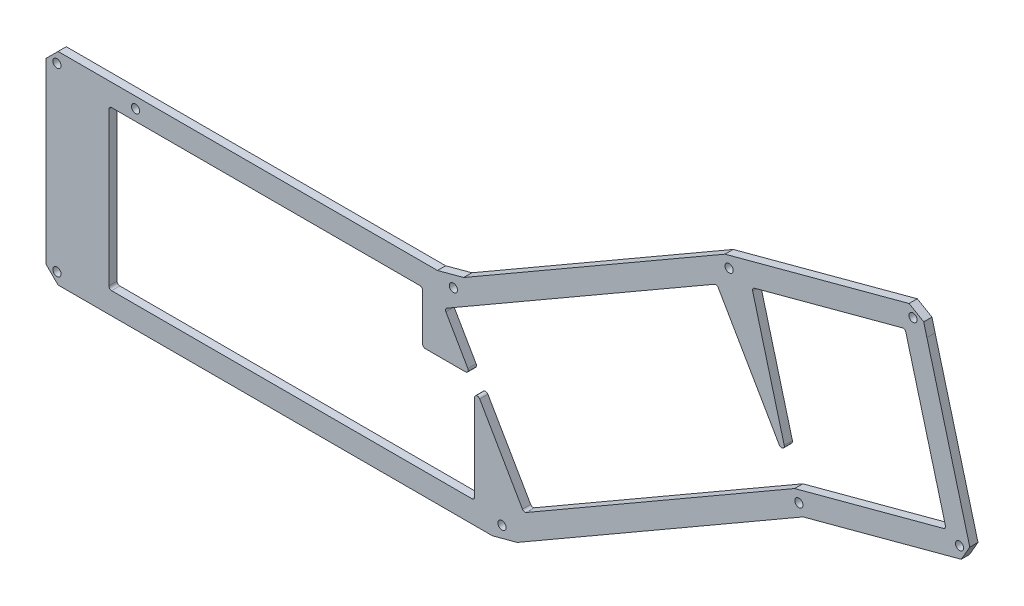
SolidWorks part; units mm, degrees
ref_plane "Plan de face" through (0, 0, 0) normal (0, 0, 1) x (1, 0, 0)
ref_plane "Plan de dessus" through (0, 0, 0) normal (0, 1, 0) x (1, 0, 0)
ref_plane "Plan de droite" through (0, 0, 0) normal (1, 0, 0) x (0, 0, -1)
sketch "Esquisse1" plane through (0, 0, 0) normal (0, 0, 1) x (1, 0, 0)
  line L0 (-73.9886, 18.0851) -> (-59.9886, 18.0851) construction
  line L1 (-73.9886, 37.0851) -> (-59.9886, 37.0851) construction
  line L2 (-73.9886, 37.0851) -> (-73.9886, 23.0851) construction
  line L3 (-73.9886, 23.0851) -> (-59.9886, 23.0851) construction
  line L4 (-59.9886, 37.0851) -> (-59.9886, 23.0851) construction
  line L5 (-73.9886, 18.0851) -> (-73.9886, 4.0851) construction
  line L6 (-73.9886, 4.0851) -> (-59.9886, 4.0851) construction
  line L7 (-59.9886, 18.0851) -> (-59.9886, 4.0851) construction
  line L8 (-73.9886, -0.9149) -> (-59.9886, -0.9149) construction
  line L9 (-73.9886, -0.9149) -> (-73.9886, -14.9149) construction
  line L10 (-73.9886, -14.9149) -> (-59.9886, -14.9149) construction
  line L11 (-59.9886, -0.9149) -> (-59.9886, -14.9149) construction
  line L12 (-73.9886, 37.0851) -> (-73.9886, 18.0851) construction
  line L13 (-54.9886, 18.0851) -> (-40.9886, 18.0851) construction
  line L14 (-54.9886, 37.0851) -> (-40.9886, 37.0851) construction
  line L15 (-54.9886, 37.0851) -> (-54.9886, 23.0851) construction
  line L16 (-54.9886, 23.0851) -> (-40.9886, 23.0851) construction
  line L17 (-40.9886, 37.0851) -> (-40.9886, 23.0851) construction
  line L18 (-54.9886, 18.0851) -> (-54.9886, 4.0851) construction
  line L19 (-54.9886, 4.0851) -> (-40.9886, 4.0851) construction
  line L20 (-40.9886, 18.0851) -> (-40.9886, 4.0851) construction
  line L21 (-54.9886, -0.9149) -> (-40.9886, -0.9149) construction
  line L22 (-54.9886, -0.9149) -> (-54.9886, -14.9149) construction
  line L23 (-54.9886, -14.9149) -> (-40.9886, -14.9149) construction
  line L24 (-40.9886, -0.9149) -> (-40.9886, -14.9149) construction
  line L25 (-54.9886, 37.0851) -> (-54.9886, 18.0851) construction
  line L26 (-35.9886, 18.0851) -> (-21.9886, 18.0851) construction
  line L27 (-35.9886, 37.0851) -> (-21.9886, 37.0851) construction
  line L28 (-35.9886, 37.0851) -> (-35.9886, 23.0851) construction
  line L29 (-35.9886, 23.0851) -> (-21.9886, 23.0851) construction
  line L30 (-21.9886, 37.0851) -> (-21.9886, 23.0851) construction
  line L31 (-35.9886, 18.0851) -> (-35.9886, 4.0851) construction
  line L32 (-35.9886, 4.0851) -> (-21.9886, 4.0851) construction
  line L33 (-21.9886, 18.0851) -> (-21.9886, 4.0851) construction
  line L34 (-35.9886, -0.9149) -> (-21.9886, -0.9149) construction
  line L35 (-35.9886, -0.9149) -> (-35.9886, -14.9149) construction
  line L36 (-35.9886, -14.9149) -> (-21.9886, -14.9149) construction
  line L37 (-21.9886, -0.9149) -> (-21.9886, -14.9149) construction
  line L38 (-35.9886, 37.0851) -> (-35.9886, 18.0851) construction
  line L39 (-16.9886, 18.0851) -> (-2.9886, 18.0851) construction
  line L40 (-16.9886, 37.0851) -> (-2.9886, 37.0851) construction
  line L41 (-16.9886, 37.0851) -> (-16.9886, 23.0851) construction
  line L42 (-16.9886, 23.0851) -> (-2.9886, 23.0851) construction
  line L43 (-2.9886, 37.0851) -> (-2.9886, 23.0851) construction
  line L44 (-16.9886, 18.0851) -> (-16.9886, 4.0851) construction
  line L45 (-16.9886, 4.0851) -> (-2.9886, 4.0851) construction
  line L46 (-2.9886, 18.0851) -> (-2.9886, 4.0851) construction
  line L47 (-16.9886, -0.9149) -> (-2.9886, -0.9149) construction
  line L48 (-16.9886, -0.9149) -> (-16.9886, -14.9149) construction
  line L49 (-16.9886, -14.9149) -> (-2.9886, -14.9149) construction
  line L50 (-2.9886, -0.9149) -> (-2.9886, -14.9149) construction
  line L51 (-16.9886, 37.0851) -> (-16.9886, 18.0851) construction
  line L52 (2.0114, 18.0851) -> (16.0114, 18.0851) construction
  line L53 (2.0114, 37.0851) -> (16.0114, 37.0851) construction
  line L54 (2.0114, 37.0851) -> (2.0114, 23.0851) construction
  line L55 (2.0114, 23.0851) -> (16.0114, 23.0851) construction
  line L56 (16.0114, 37.0851) -> (16.0114, 23.0851) construction
  line L57 (2.0114, 18.0851) -> (2.0114, 4.0851) construction
  line L58 (2.0114, 4.0851) -> (16.0114, 4.0851) construction
  line L59 (16.0114, 18.0851) -> (16.0114, 4.0851) construction
  line L60 (2.0114, -0.9149) -> (16.0114, -0.9149) construction
  line L61 (2.0114, -0.9149) -> (2.0114, -14.9149) construction
  line L62 (2.0114, -14.9149) -> (16.0114, -14.9149) construction
  line L63 (16.0114, -0.9149) -> (16.0114, -14.9149) construction
  line L64 (2.0114, 37.0851) -> (2.0114, 18.0851) construction
  line L65 (21.0114, 18.0851) -> (35.0114, 18.0851) construction
  line L66 (21.0114, 37.0851) -> (35.0114, 37.0851) construction
  line L67 (21.0114, 37.0851) -> (21.0114, 23.0851) construction
  line L68 (21.0114, 23.0851) -> (35.0114, 23.0851) construction
  line L69 (35.0114, 37.0851) -> (35.0114, 23.0851) construction
  line L70 (21.0114, 18.0851) -> (21.0114, 4.0851) construction
  line L71 (21.0114, 4.0851) -> (35.0114, 4.0851) construction
  line L72 (35.0114, 18.0851) -> (35.0114, 4.0851) construction
  line L73 (21.0114, -0.9149) -> (35.0114, -0.9149) construction
  line L74 (21.0114, -0.9149) -> (21.0114, -14.9149) construction
  line L75 (21.0114, -14.9149) -> (35.0114, -14.9149) construction
  line L76 (35.0114, -0.9149) -> (35.0114, -14.9149) construction
  line L77 (21.0114, 37.0851) -> (21.0114, 18.0851) construction
  line L78 (40.0114, 18.0851) -> (54.0114, 18.0851) construction
  line L81 (-76.7538, 39.0851) -> (-76.7538, -16.9149)
  line L82 (-95.7538, 44.0851) -> (-53.0442, 44.0851) construction
  line L83 (40.0114, 18.0851) -> (40.0114, 4.0851) construction
  line L84 (40.0114, 4.0851) -> (54.0114, 4.0851) construction
  line L85 (54.0114, 18.0851) -> (54.0114, 4.0851) construction
  line L86 (40.0114, -0.9149) -> (54.0114, -0.9149) construction
  line L87 (40.0114, -0.9149) -> (40.0114, -14.9149) construction
  line L88 (40.0114, -14.9149) -> (54.0114, -14.9149) construction
  line L89 (54.0114, -0.9149) -> (54.0114, -14.9149) construction
  line L90 (40.0114, 20.0851) -> (40.0114, 18.0851) construction
  line L91 (-73.9886, 18.0851) -> (-54.9886, 18.0851) construction
  line L92 (56.0114, 20.0851) -> (56.7532, 18.8002) construction
  line L93 (-66.9886, 37.0851) -> (-66.9886, 44.0851) construction
  line L94 (67.3933, 2.371) -> (74.3933, -9.7534) construction
  line L95 (146.1202, 94.012) -> (168.4398, 55.3534)
  line L96 (158.7183, 99.2303) -> (170.2717, 56.1122)
  line L97 (19.0114, 39.0851) -> (37.0114, 39.0851) construction
  line L98 (37.0114, 39.0851) -> (37.0114, 21.0851) construction
  line L99 (19.0114, 21.0851) -> (37.0114, 21.0851) construction
  line L100 (19.0114, 39.0851) -> (19.0114, 21.0851) construction
  line L101 (79.4363, 55.512) -> (88.4363, 39.9235) construction
  line L102 (88.4363, 39.9235) -> (72.8478, 30.9235) construction
  line L103 (63.8478, 46.512) -> (72.8478, 30.9235) construction
  line L104 (79.4363, 55.512) -> (63.8478, 46.512) construction
  line L105 (62.9818, 46.012) -> (71.9818, 30.4235) construction
  line L106 (71.9818, 30.4235) -> (56.3933, 21.4235) construction
  line L107 (47.3933, 37.012) -> (56.3933, 21.4235) construction
  line L108 (62.9818, 46.012) -> (47.3933, 37.012) construction
  line L109 (164.2542, 60.603) -> (148.6657, 51.603) construction
  line L110 (62.2497, 43.2799) -> (71.7497, 26.8254) construction
  line L111 (78.7042, 52.7799) -> (88.2042, 36.3254) construction
  line L112 (95.1587, 62.2799) -> (104.6587, 45.8254) construction
  line L113 (111.6132, 71.7799) -> (121.1132, 55.3254) construction
  line L114 (128.0677, 81.2799) -> (137.5677, 64.8254) construction
  line L115 (144.5221, 90.7799) -> (154.0221, 74.3254) construction
  line L116 (148.6657, 51.603) -> (157.6657, 36.0146) construction
  line L117 (69.1254, 3.371) -> (76.1254, -8.7534) construction
  line L118 (88.2497, -1.7534) -> (76.1254, -8.7534) construction
  line L119 (81.2497, 10.371) -> (88.2497, -1.7534) construction
  line L120 (81.2497, 10.371) -> (69.1254, 3.371) construction
  line L121 (59.6254, 19.8254) -> (66.6254, 7.7011) construction
  line L122 (78.7497, 14.7011) -> (66.6254, 7.7011) construction
  line L123 (71.7497, 26.8254) -> (78.7497, 14.7011) construction
  line L124 (50.1254, 36.2799) -> (57.1254, 24.1556) construction
  line L125 (69.2497, 31.1556) -> (57.1254, 24.1556) construction
  line L126 (62.2497, 43.2799) -> (69.2497, 31.1556) construction
  line L127 (62.2497, 43.2799) -> (50.1254, 36.2799) construction
  line L128 (71.7497, 26.8254) -> (59.6254, 19.8254) construction
  line L129 (85.5799, 12.871) -> (92.5799, 0.7466) construction
  line L130 (104.7042, 7.7466) -> (92.5799, 0.7466) construction
  line L131 (97.7042, 19.871) -> (104.7042, 7.7466) construction
  line L132 (97.7042, 19.871) -> (85.5799, 12.871) construction
  line L133 (76.0799, 29.3254) -> (83.0799, 17.2011) construction
  line L134 (95.2042, 24.2011) -> (83.0799, 17.2011) construction
  line L135 (88.2042, 36.3254) -> (95.2042, 24.2011) construction
  line L136 (66.5799, 45.7799) -> (73.5799, 33.6556) construction
  line L137 (85.7042, 40.6556) -> (73.5799, 33.6556) construction
  line L138 (78.7042, 52.7799) -> (85.7042, 40.6556) construction
  line L139 (78.7042, 52.7799) -> (66.5799, 45.7799) construction
  line L140 (88.2042, 36.3254) -> (76.0799, 29.3254) construction
  line L141 (102.0343, 22.371) -> (109.0343, 10.2466) construction
  line L142 (121.1587, 17.2466) -> (109.0343, 10.2466) construction
  line L143 (114.1587, 29.371) -> (121.1587, 17.2466) construction
  line L144 (114.1587, 29.371) -> (102.0343, 22.371) construction
  line L145 (92.5343, 38.8254) -> (99.5343, 26.7011) construction
  line L146 (111.6587, 33.7011) -> (99.5343, 26.7011) construction
  line L147 (104.6587, 45.8254) -> (111.6587, 33.7011) construction
  line L148 (83.0343, 55.2799) -> (90.0343, 43.1556) construction
  line L149 (102.1587, 50.1556) -> (90.0343, 43.1556) construction
  line L150 (95.1587, 62.2799) -> (102.1587, 50.1556) construction
  line L151 (95.1587, 62.2799) -> (83.0343, 55.2799) construction
  line L152 (104.6587, 45.8254) -> (92.5343, 38.8254) construction
  line L153 (118.4888, 31.871) -> (125.4888, 19.7466) construction
  line L154 (137.6132, 26.7466) -> (125.4888, 19.7466) construction
  line L155 (130.6132, 38.871) -> (137.6132, 26.7466) construction
  line L156 (130.6132, 38.871) -> (118.4888, 31.871) construction
  line L157 (108.9888, 48.3254) -> (115.9888, 36.2011) construction
  line L158 (128.1132, 43.2011) -> (115.9888, 36.2011) construction
  line L159 (121.1132, 55.3254) -> (128.1132, 43.2011) construction
  line L160 (99.4888, 64.7799) -> (106.4888, 52.6556) construction
  line L161 (118.6132, 59.6556) -> (106.4888, 52.6556) construction
  line L162 (111.6132, 71.7799) -> (118.6132, 59.6556) construction
  line L163 (111.6132, 71.7799) -> (99.4888, 64.7799) construction
  line L164 (121.1132, 55.3254) -> (108.9888, 48.3254) construction
  line L165 (134.9433, 41.371) -> (141.9433, 29.2466) construction
  line L166 (154.0677, 36.2466) -> (141.9433, 29.2466) construction
  line L167 (147.0677, 48.371) -> (154.0677, 36.2466) construction
  line L168 (147.0677, 48.371) -> (134.9433, 41.371) construction
  line L169 (125.4433, 57.8254) -> (132.4433, 45.7011) construction
  line L170 (144.5677, 52.7011) -> (132.4433, 45.7011) construction
  line L171 (137.5677, 64.8254) -> (144.5677, 52.7011) construction
  line L172 (115.9433, 74.2799) -> (122.9433, 62.1556) construction
  line L173 (135.0677, 69.1556) -> (122.9433, 62.1556) construction
  line L174 (128.0677, 81.2799) -> (135.0677, 69.1556) construction
  line L175 (128.0677, 81.2799) -> (115.9433, 74.2799) construction
  line L176 (137.5677, 64.8254) -> (125.4433, 57.8254) construction
  line L177 (151.3978, 50.871) -> (158.3978, 38.7466) construction
  line L178 (170.5221, 45.7466) -> (158.3978, 38.7466) construction
  line L179 (163.5221, 57.871) -> (170.5221, 45.7466) construction
  line L180 (163.5221, 57.871) -> (151.3978, 50.871) construction
  line L181 (141.8978, 67.3254) -> (148.8978, 55.2011) construction
  line L182 (161.0221, 62.2011) -> (148.8978, 55.2011) construction
  line L183 (154.0221, 74.3254) -> (161.0221, 62.2011) construction
  line L184 (132.3978, 83.7799) -> (139.3978, 71.6556) construction
  line L185 (151.5221, 78.6556) -> (139.3978, 71.6556) construction
  line L186 (144.5221, 90.7799) -> (151.5221, 78.6556) construction
  line L187 (144.5221, 90.7799) -> (132.3978, 83.7799) construction
  line L188 (154.0221, 74.3254) -> (141.8978, 67.3254) construction
  line L189 (173.2542, 45.0146) -> (157.6657, 36.0146) construction
  line L190 (164.2542, 60.603) -> (173.2542, 45.0146) construction
  line L191 (178.3169, 34.0986) -> (169.0534, 56.4627) construction
  line L192 (169.5193, 62.7839) -> (174.1781, 45.3972) construction
  line L193 (174.1781, 45.3972) -> (191.5647, 50.056) construction
  line L194 (186.906, 67.4426) -> (191.5647, 50.056) construction
  line L195 (162.1337, 98.0749) -> (167.0513, 79.7223) construction
  line L196 (169.5193, 62.7839) -> (186.906, 67.4426) construction
  line L197 (167.0513, 79.7223) -> (180.5742, 83.3457) construction
  line L198 (162.1337, 98.0749) -> (175.6567, 101.6983) construction
  line L199 (162.1337, 98.0749) -> (165.7572, 84.5519) construction
  line L200 (165.7572, 84.5519) -> (179.2801, 88.1754) construction
  line L201 (175.6567, 101.6983) -> (179.2801, 88.1754) construction
  line L202 (167.0513, 79.7223) -> (170.6747, 66.1993) construction
  line L203 (170.6747, 66.1993) -> (184.1977, 69.8228) construction
  line L204 (180.5742, 83.3457) -> (184.1977, 69.8228) construction
  line L205 (171.9688, 61.3697) -> (185.4918, 64.9932) construction
  line L206 (171.9688, 61.3697) -> (175.5923, 47.8467) construction
  line L207 (175.5923, 47.8467) -> (189.1152, 51.4702) construction
  line L208 (185.4918, 64.9932) -> (189.1152, 51.4702) construction
  line L209 (185.4038, 84.6398) -> (198.9268, 88.2633) construction
  line L210 (180.4863, 102.9924) -> (194.0092, 106.6159) construction
  line L211 (180.4863, 102.9924) -> (184.1097, 89.4695) construction
  line L212 (184.1097, 89.4695) -> (197.6327, 93.0929) construction
  line L213 (194.0092, 106.6159) -> (197.6327, 93.0929) construction
  line L214 (185.4038, 84.6398) -> (189.0273, 71.1169) construction
  line L215 (189.0273, 71.1169) -> (202.5503, 74.7403) construction
  line L216 (198.9268, 88.2633) -> (202.5503, 74.7403) construction
  line L217 (190.3214, 66.2873) -> (203.8444, 69.9107) construction
  line L218 (190.3214, 66.2873) -> (193.9449, 52.7643) construction
  line L219 (193.9449, 52.7643) -> (207.4678, 56.3878) construction
  line L220 (203.8444, 69.9107) -> (207.4678, 56.3878) construction
  line L221 (187.8719, 67.7015) -> (192.5307, 50.3148) construction
  line L222 (192.5307, 50.3148) -> (209.9173, 54.9735) construction
  line L223 (205.2586, 72.3602) -> (209.9173, 54.9735) construction
  line L224 (180.4863, 102.9924) -> (185.4038, 84.6398) construction
  line L225 (187.8719, 67.7015) -> (205.2586, 72.3602) construction
  line L226 (203.7564, 89.5574) -> (217.2794, 93.1809) construction
  line L227 (198.8389, 107.91) -> (212.3618, 111.5335) construction
  line L228 (198.8389, 107.91) -> (202.4623, 94.387) construction
  line L229 (202.4623, 94.387) -> (215.9853, 98.0105) construction
  line L230 (212.3618, 111.5335) -> (215.9853, 98.0105) construction
  line L231 (203.7564, 89.5574) -> (207.3799, 76.0344) construction
  line L232 (207.3799, 76.0344) -> (220.9029, 79.6579) construction
  line L233 (217.2794, 93.1809) -> (220.9029, 79.6579) construction
  line L234 (208.674, 71.2048) -> (222.197, 74.8283) construction
  line L235 (208.674, 71.2048) -> (212.2975, 57.6819) construction
  line L236 (212.2975, 57.6819) -> (225.8204, 61.3053) construction
  line L237 (222.197, 74.8283) -> (225.8204, 61.3053) construction
  line L238 (206.2245, 72.619) -> (210.8833, 55.2324) construction
  line L239 (210.8833, 55.2324) -> (228.2699, 59.8911) construction
  line L240 (223.6112, 77.2778) -> (228.2699, 59.8911) construction
  line L241 (198.8389, 107.91) -> (203.7564, 89.5574) construction
  line L242 (206.2245, 72.619) -> (223.6112, 77.2778) construction
  line L243 (167.0513, 79.7223) -> (185.4038, 84.6398) construction
  line L244 (38.0114, 20.0851) -> (56.0114, 20.0851) construction
  line L245 (56.0114, 20.0851) -> (56.0114, 2.0851) construction
  line L246 (38.0114, 2.0851) -> (56.0114, 2.0851) construction
  line L247 (38.0114, 20.0851) -> (38.0114, 2.0851) construction
  line L248 (72.4818, 29.5575) -> (56.8933, 20.5575) construction
  line L249 (56.8933, 20.5575) -> (65.8933, 4.969) construction
  line L250 (81.4818, 13.969) -> (65.8933, 4.969) construction
  line L251 (72.4818, 29.5575) -> (81.4818, 13.969) construction
  line L252 (56.8933, 20.5575) -> (57.6111, 19.3142) construction
  line L253 (164.6018, 81.1365) -> (169.2605, 63.7498) construction
  line L254 (169.2605, 63.7498) -> (186.6472, 68.4086) construction
  line L255 (181.9884, 85.7952) -> (186.6472, 68.4086) construction
  line L256 (164.6018, 81.1365) -> (181.9884, 85.7952) construction
  line L257 (154.7542, 77.0575) -> (163.7542, 61.469) construction
  line L258 (163.7542, 61.469) -> (148.1657, 52.469) construction
  line L259 (139.1657, 68.0575) -> (148.1657, 52.469) construction
  line L260 (154.7542, 77.0575) -> (139.1657, 68.0575) construction
  line L261 (196.3894, 109.3242) -> (213.776, 113.983) construction
  line L262 (-94.7538, 35.7952) -> (-76.7538, 35.7952) construction
  line L263 (-94.7538, 35.7952) -> (-94.7538, 2.7952) construction
  line L264 (-94.7538, 2.7952) -> (-76.7538, 2.7952) construction
  line L266 (213.776, 113.983) -> (218.4348, 96.5963) construction
  line L267 (201.0481, 91.9375) -> (218.4348, 96.5963) construction
  line L268 (196.3894, 109.3242) -> (201.0481, 91.9375) construction
  line L269 (-75.9886, -16.9149) -> (-57.9886, -16.9149) construction
  line L270 (-57.9886, 1.0851) -> (-57.9886, -16.9149) construction
  line L271 (-75.9886, 1.0851) -> (-57.9886, 1.0851) construction
  line L272 (-75.9886, 1.0851) -> (-75.9886, -16.9149) construction
  line L273 (38.0114, -16.9149) -> (56.0114, -16.9149) construction
  line L274 (56.0114, 1.0851) -> (56.0114, -16.9149) construction
  line L275 (38.0114, 1.0851) -> (56.0114, 1.0851) construction
  line L276 (38.0114, 1.0851) -> (38.0114, -16.9149) construction
  line L277 (-75.9886, 39.0851) -> (-57.9886, 39.0851) construction
  line L278 (-57.9886, 39.0851) -> (-57.9886, 21.0851) construction
  line L279 (-75.9886, 21.0851) -> (-57.9886, 21.0851) construction
  line L280 (-75.9886, 39.0851) -> (-75.9886, 21.0851) construction
  line L281 (145.2542, 93.512) -> (129.6657, 84.512) construction
  line L282 (129.6657, 84.512) -> (138.6657, 68.9235) construction
  line L283 (154.2542, 77.9235) -> (138.6657, 68.9235) construction
  line L284 (145.2542, 93.512) -> (154.2542, 77.9235) construction
  line L285 (223.4353, 116.5711) -> (228.0941, 99.1845) construction
  line L286 (148.2159, 106.7689) -> (211.1879, 123.6422) construction
  line L287 (177.5508, 35.9482) -> (235.6877, 51.5259) construction
  line L288 (177.5508, 35.9482) -> (72.9989, -24.4149) construction
  line L289 (-95.7538, -26.9149) -> (63.6687, -26.9149) construction
  line L290 (-100.7538, 35.7952) -> (-100.7538, -21.9149) construction
  line L291 (-75.9886, 49.0851) -> (43.3046, 49.0851) construction
  line L292 (148.2159, 106.7689) -> (52.6347, 51.5851) construction
  line L293 (-75.9886, 49.0851) -> (-57.9886, 49.0851) construction
  line L294 (140.2542, 102.1722) -> (124.6657, 93.1722) construction
  line L295 (193.8012, 118.9835) -> (211.1879, 123.6422) construction
  line L296 (213.4714, 45.5731) -> (230.8581, 50.2318) construction
  line L297 (38.0114, -26.9149) -> (38.0114, -85.4624) construction
  line L298 (178.2542, 36.3543) -> (162.6657, 27.3543) construction
  line L299 (38.0114, -26.9149) -> (56.0114, -26.9149) construction
  line L300 (-100.7538, 2.7952) -> (-100.7538, -38.0419) construction
  line L301 (-100.7538, 35.7952) -> (-100.7538, 2.7952) construction
  line L302 (-75.9886, 49.0851) -> (-95.7538, 49.0851) construction
  line L303 (-100.7538, 44.0851) -> (-100.7538, 35.7952) construction
  line L304 (211.1879, 123.6422) -> (216.0732, 124.9512) construction
  line L305 (222.1691, 121.4083) -> (223.4353, 116.5711) construction
  line L306 (228.0941, 99.1845) -> (239.2233, 57.6497) construction
  line L307 (216.0732, 124.9512) -> (222.1691, 121.4083) construction
  line L308 (235.6877, 51.5259) -> (239.2233, 57.6497) construction
  line L309 (63.6687, -26.9149) -> (72.9989, -24.4149) construction
  line L310 (52.6347, 51.5851) -> (43.3046, 49.0851) construction
  line L311 (-95.7538, 49.0851) -> (-100.7538, 44.0851) construction
  line L312 (-100.7538, -21.9149) -> (-95.7538, -26.9149) construction
  line L313 (-95.7538, 49.0851) -> (-95.7538, 44.0851) construction
  line L314 (-95.7538, 44.0851) -> (-100.7538, 44.0851) construction
  line L315 (-95.7538, -26.9149) -> (-95.7538, -21.9149) construction
  line L316 (68.3338, -25.6649) -> (67.0397, -20.8353) construction
  line L317 (47.9697, 50.3351) -> (49.2637, 45.5055) construction
  line L318 (177.5508, 35.9482) -> (175.6374, 40.5676) construction
  line L319 (148.2159, 106.7689) -> (150.1293, 102.1495) construction
  line L320 (239.2233, 57.6497) -> (234.3936, 56.3556) construction
  line L321 (216.0732, 124.9512) -> (217.3634, 120.1206) construction
  line L322 (146.1202, 94.012) -> (155.1202, 78.4235) construction
  line L323 (-76.7538, 35.7952) -> (-96.7538, 35.7952) construction
  line L324 (148.6019, 105.8371) -> (53.0207, 50.6533)
  line L325 (163.6358, 80.8777) -> (168.2946, 63.491) construction
  line L326 (57.0114, 14.621) -> (57.0114, -16.9149)
  line L328 (-96.7538, 39.0851) -> (-96.7538, 1.0851) construction
  line L329 (53.0207, 50.6533) -> (43.4362, 48.0851)
  line L330 (-75.9886, 48.0851) -> (43.4362, 48.0851)
  line L331 (-75.9886, 48.0851) -> (-95.3395, 48.0851)
  line L332 (-95.3395, 48.0851) -> (-99.7538, 43.6709)
  line L333 (-99.7538, 43.6709) -> (-99.7538, 35.7952)
  line L334 (-99.7538, 35.7952) -> (-99.7538, -21.5007)
  line L335 (-99.7538, -21.5007) -> (-95.3395, -25.9149)
  line L336 (-95.3395, -25.9149) -> (63.5371, -25.9149)
  line L337 (63.5371, -25.9149) -> (72.6129, -23.483)
  line L338 (177.1648, 36.88) -> (72.6129, -23.483)
  line L339 (177.1648, 36.88) -> (235.0288, 52.3847)
  line L340 (235.0288, 52.3847) -> (238.1501, 57.7909)
  line L341 (227.1281, 98.9257) -> (238.1501, 57.7909)
  line L342 (222.4686, 116.3151) -> (227.1281, 98.9257)
  line L343 (221.307, 120.7527) -> (222.4686, 116.3151)
  line L344 (215.9303, 123.8777) -> (221.307, 120.7527)
  line L345 (211.4467, 122.6763) -> (215.9303, 123.8777)
  line L346 (148.6019, 105.8371) -> (211.4467, 122.6763)
  line L347 (214.742, 114.2418) -> (229.2358, 60.1499)
  line L348 (174.0769, 44.3349) -> (228.5287, 58.9252)
  line L349 (174.0769, 44.3349) -> (75.8933, -12.3515)
  line L350 (159.4254, 100.455) -> (213.5172, 114.9489)
  line L351 (144.7542, 94.378) -> (46.8933, 37.878)
  line L352 (-75.7538, -17.9149) -> (56.0114, -17.9149)
  line L353 (-75.7538, 40.0851) -> (37.0114, 40.0851)
  line L354 (2.0114, 40.0851) -> (16.0114, 40.0851) construction
  line L355 (126.5677, 83.878) -> (114.4433, 76.878) construction
  line L356 (179.7098, 105.8902) -> (193.2328, 109.5137) construction
  line L357 (215.2596, 112.3099) -> (218.8831, 98.787) construction
  line L358 (194.7213, 49.8665) -> (208.2443, 53.49) construction
  line L359 (155.5677, 33.6485) -> (143.4433, 26.6485) construction
  line L360 (40.0114, -17.9149) -> (54.0114, -17.9149) construction
  line L361 (58.8774, 15.121) -> (74.5273, -11.9854)
  line L362 (66.5273, 1.871) -> (73.5273, -10.2534) construction
  line L363 (40.0114, 37.0851) -> (40.0114, 23.0851) construction
  line L364 (57.0114, 1.0851) -> (57.0114, -16.9149) construction
  line L365 (46.5273, 36.512) -> (54.568, 22.5851)
  line L366 (51.52, 37.0851) -> (54.0114, 37.0851) construction
  line L367 (40.0114, 23.0851) -> (54.0114, 23.0851) construction
  line L368 (39.0114, 21.0851) -> (53.702, 21.0851)
  line L369 (54.0114, 29.5492) -> (54.0114, 25.5492) construction
  line L370 (38.0114, 39.0851) -> (38.0114, 22.0851)
  line L371 (38.0114, 39.0851) -> (38.0114, 21.0851) construction
  line L372 (46.5273, 36.512) -> (55.5273, 20.9235) construction
  line L374 (38.0114, 21.0851) -> (56.0114, 21.0851) construction
  circle A0 centre (-95.7538, 44.0851) radius 1.5
  circle A1 centre (-95.7538, -21.9149) radius 1.5
  circle A2 centre (67.0397, -20.8353) radius 1.5
  circle A3 centre (49.2637, 45.5055) radius 1.5
  circle A4 centre (175.6374, 40.5676) radius 1.5
  circle A5 centre (150.1293, 102.1495) radius 1.5
  circle A6 centre (234.3936, 56.3556) radius 1.5
  circle A7 centre (217.3634, 120.1206) radius 1.5
  circle A8 centre (-66.9886, 44.0851) radius 1.5
  arc A9 (168.4398, 55.3534) -> (170.2717, 56.1122) centre (169.3058, 55.8534) ccw
  arc A10 (57.0114, 14.621) -> (58.8774, 15.121) centre (58.0114, 14.621) cw
  arc A11 (53.702, 21.0851) -> (54.568, 22.5851) centre (53.702, 22.0851) ccw
  arc A12 (39.0114, 21.0851) -> (38.0114, 22.0851) centre (39.0114, 22.0851) cw
  arc A13 (-75.7538, 40.0851) -> (-76.7538, 39.0851) centre (-75.7538, 39.0851) ccw
  arc A16 (-76.7538, -16.9149) -> (-75.7538, -17.9149) centre (-75.7538, -16.9149) ccw
  arc A17 (228.5287, 58.9252) -> (229.2358, 60.1499) centre (228.2699, 59.8911) ccw
  arc A18 (214.742, 114.2418) -> (213.5172, 114.9489) centre (213.776, 113.983) ccw
  arc A19 (158.7183, 99.2303) -> (159.4254, 100.455) centre (159.6842, 99.4891) cw
  arc A20 (146.1202, 94.012) -> (144.7542, 94.378) centre (145.2542, 93.512) ccw
  arc A21 (57.0114, -16.9149) -> (56.0114, -17.9149) centre (56.0114, -16.9149) cw
  arc A22 (74.5273, -11.9854) -> (75.8933, -12.3515) centre (75.3933, -11.4854) ccw
  arc A23 (46.5273, 36.512) -> (46.8933, 37.878) centre (47.3933, 37.012) cw
  arc A24 (38.0114, 39.0851) -> (37.0114, 40.0851) centre (37.0114, 39.0851) ccw
  point P85 (40.0114, 37.0851)
  point P86 (54.0114, 23.0851)
  point P88 (54.0114, 37.0851)
  point P102 (38.0114, 39.0851)
  point P103 (56.0114, 39.0851)
  point P304 (48.3046, 49.0851)
  point P305 (240.5174, 52.82)
  point P308 (68.6687, -26.9149)
  point P309 (-100.7538, -26.9149)
  point P311 (-100.7538, 49.0851)
  point P312 (220.9029, 126.2453)
  point P409 (172.2377, 48.7752)
  dimension "D32" = 3
  dimension "D33" = 5
  dimension "D40" = 5
  dimension "D41" = 5
  dimension "D42" = 5
  dimension "D43" = 5
  dimension "D44" = 20
  dimension "D53" = 2
  dimension "D56" = 1
  dimension "D59" = 1
  dimension "D63" = 1
  dimension "D64" = 1
  dimension "D8" = 1
  dimension "D1" = 14
  dimension "D2" = 14
  dimension "D4" = 19
  dimension "D6" = 19
  dimension "D7" = 30
  dimension "D10" = 1
  dimension "D11" = 2
  dimension "D13" = 0.5
  dimension "D15" = 2
  dimension "D12" = 7.5
  dimension "D14" = 19
  dimension "D18" = 2
  dimension "D20" = 18
  dimension "D21" = 33
  dimension "D22" = 2
  dimension "D9" = 2
  dimension "D16" = 2
  dimension "D19" = 2
  dimension "D23" = 2
  dimension "D24" = 10
  dimension "D25" = 10
  dimension "D26" = 10
  dimension "D27" = 10
  dimension "D28" = 10
  dimension "D29" = 6
  dimension "D30" = 10
  dimension "D31" = 10
  dimension "D45" = 1
  dimension "D46" = 3
  dimension "D47" = 3
  dimension "D48" = 3
  dimension "D49" = 3
  dimension "D50" = 3
  dimension "D51" = 3
  dimension "D52" = 3
  dimension "D54" = 1
  dimension "D55" = 1
  dimension "D57" = 1
  dimension "D58" = 1
  dimension "D60" = 1
  dimension "D61" = 1
  dimension "D62" = 1
  dimension "D3" = 3
  dimension "D5" = 7
  dimension "D17" = 3
extrude "Boss.-Extru.1" add sketch "Esquisse1" along normal blind 3
